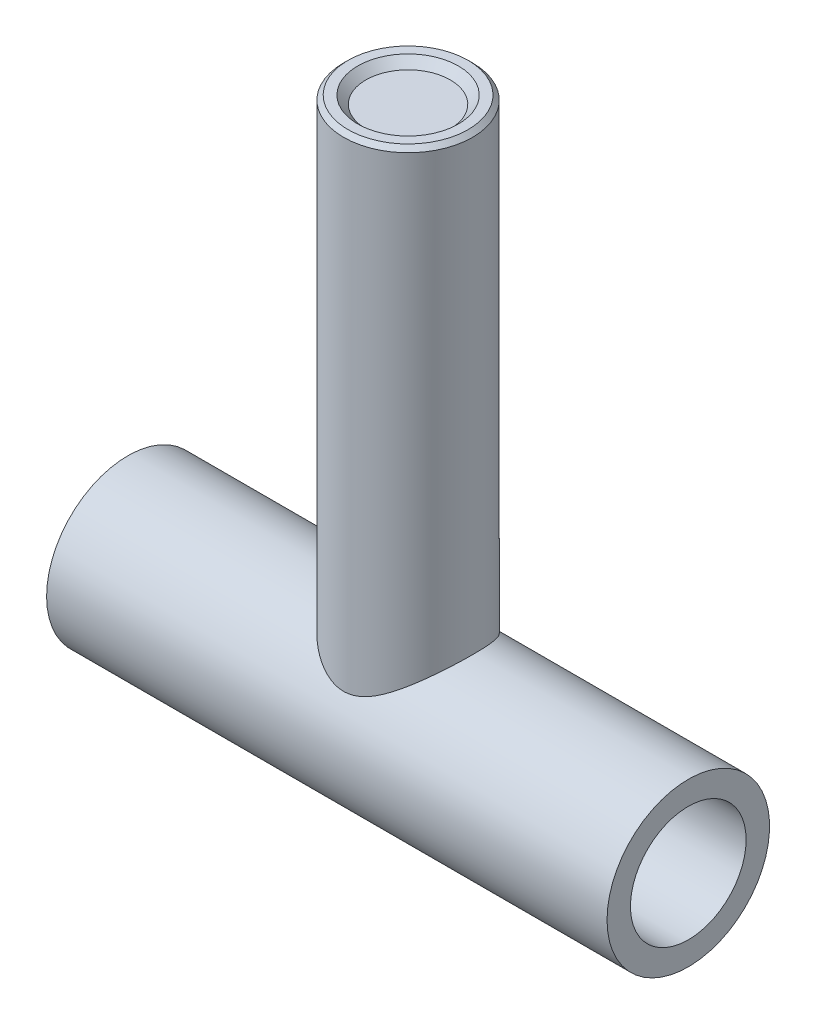
SolidWorks part; units mm, degrees
ref_plane "Front Plane" through (0, 0, 0) normal (0, 0, 1) x (1, 0, 0)
ref_plane "Top Plane" through (0, 0, 0) normal (0, 1, 0) x (1, 0, 0)
ref_plane "Right Plane" through (0, 0, 0) normal (1, 0, 0) x (0, 0, -1)
ref_plane "Plane1" through (0, 0, 0) normal (0, 0, -1) x (-1, 0, 0)
sketch "Sketch1" plane through (0, 0, 0) normal (0, 0, -1) x (-1, 0, 0)
  line L0 (-63, 18.27) -> (-63, 0)
  line L1 (-63, 0) -> (63, 0)
  line L2 (63, 0) -> (63, 18.27)
  line L3 (63, 18.27) -> (-63, 18.27)
  line L4 (-63, 0) -> (63, 0) construction
  dimension "D1" = 126
revolve "Revolve1" add sketch "Sketch1" angle 360 about L4 reverse direction yes
hole_wizard "M22 Clearance Hole1" positions "Sketch3" profile "Sketch2" hole size "M22" standard "ANSI Metric"
sketch "Sketch3" plane through (63, 0, 0) normal (1, 0, 0) x (0, 0, -1)
  point P0 (0, 0)
sketch "Sketch2" plane through (63, 0, 0) normal (0, 1, 0) x (0, 0, -1)
  line L0 (0, 0) -> (0, 126)
  line L1 (0, 126) -> (13, 126)
  line L2 (13, 126) -> (13, 0)
  line L5 (13, 0) -> (0, 0)
  line L11 (0, -6.35) -> (0, 107.95) construction
  dimension "Thru Hole Dia." = 26
  dimension "Thru Hole Depth" = 126
ref_plane "Plane2" through (0, 120, 0) normal (0, 1, 0) x (1, 0, 0)
sketch "Sketch4" plane through (0, 120, 0) normal (0, 1, 0) x (1, 0, 0)
  circle A0 centre (0, 0) radius 14.5
extrude "Boss-Extrude1" add sketch "Sketch4" against normal up to next
ref_plane "Plane3" through (0, 18.5, 0) normal (0, 1, 0) x (1, 0, 0)
sketch "Sketch5" plane through (0, 18.5, 0) normal (0, 1, 0) x (1, 0, 0)
  circle A0 centre (0, 0) radius 13
extrude "Cut-Extrude1" cut sketch "Sketch5" against normal up to next
sketch "Sketch6" plane through (0, 18.5, 0) normal (0, -1, 0) x (1, 0, 0)
  circle A0 centre (0, 0) radius 9.0974
extrude "Cut-Extrude2" cut sketch "Sketch6" against normal blind 0.4 draft 70
sketch "Sketch7" plane through (0, 18.9, 0) normal (0, -1, 0) x (1, 0, 0)
  circle A0 centre (0, 0) radius 7.9984
extrude "Cut-Extrude3" cut sketch "Sketch7" against normal blind 1.26 draft 50 draft outward yes
sketch "Sketch8" plane through (0, 20.16, 0) normal (0, -1, 0) x (1, 0, 0)
  circle A0 centre (0, 0) radius 9.5
extrude "Cut-Extrude4" cut sketch "Sketch8" against normal blind 30.5245
sketch "Sketch9" plane through (0, 120, 0) normal (0, 1, 0) x (-1, 0, 0)
  circle A0 centre (0, 0) radius 11.3155
extrude "Cut-Extrude5" cut sketch "Sketch9" against normal blind 1.8155 draft 45
chamfer "Chamfer1" distance 1 angle 45 1 edges at (0, 120, -14.5)
fillet "Fillet1" radius 3.2 1 edges at (0, 18.5, -13) tangent propagation no
